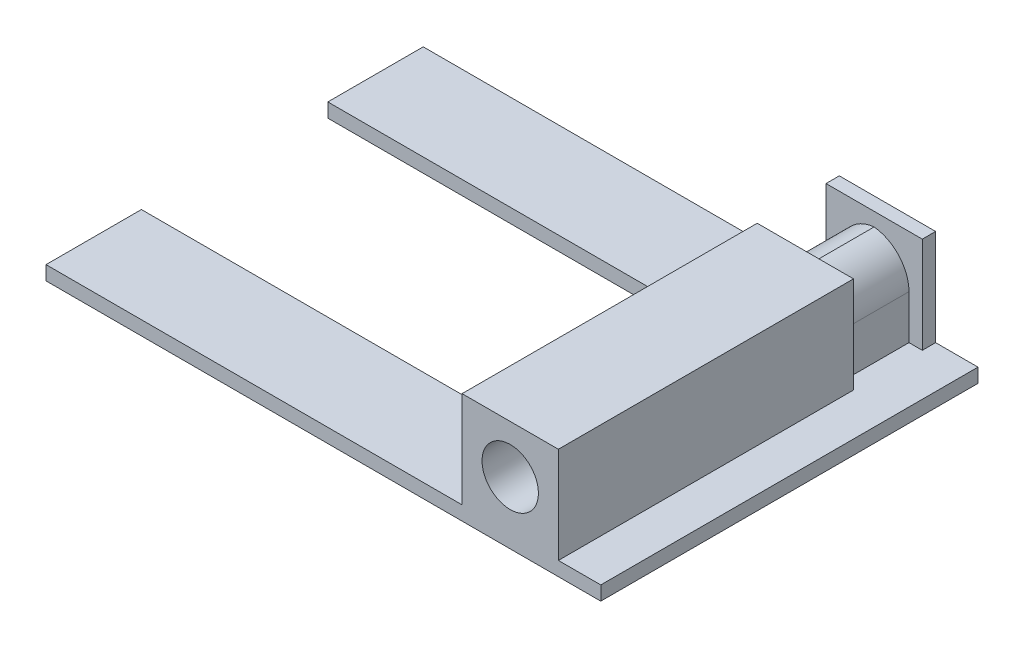
SolidWorks part; units mm, degrees
ref_plane "Front Plane" through (0, 0, 0) normal (0, 0, 1) x (1, 0, 0)
ref_plane "Top Plane" through (0, 0, 0) normal (0, 1, 0) x (1, 0, 0)
ref_plane "Right Plane" through (0, 0, 0) normal (1, 0, 0) x (0, 0, -1)
sketch "Sketch1" plane through (0, 0, 0) normal (0, 1, 0) x (1, 0, 0)
  line L0 (-367.5496, 171.2119) -> (132.4504, 171.2119)
  line L1 (132.4504, 171.2119) -> (132.4504, -168.7881)
  line L2 (132.4504, -168.7881) -> (-367.5496, -168.7881)
  line L3 (-485, 3.2119) -> (-117.5496, -168.7881) construction
  line L4 (0, -0.7881) -> (-367.5496, -168.7881) construction
  line L5 (-301.2748, -82.7881) -> (-367.5496, -82.7881) construction
  line L6 (0, -0.7881) -> (132.4504, -168.7881) construction
  line L7 (-367.5496, -82.7881) -> (132.4504, -82.7881) construction
  line L8 (-367.5496, 171.2119) -> (0, -0.7881) construction
  line L9 (-117.5496, 171.2119) -> (-485, 3.2119) construction
  line L10 (-183.7748, 85.2119) -> (-367.5496, 85.2119) construction
  line L11 (0, -0.7881) -> (132.4504, 171.2119) construction
  line L12 (-183.7748, 85.2119) -> (132.4504, 85.2119) construction
  line L13 (-367.5496, 171.2119) -> (-367.5496, 85.2119)
  line L14 (-117.5496, 171.2119) -> (132.4504, 85.2119) construction
  line L15 (132.4504, 171.2119) -> (0, 85.2119) construction
  line L16 (132.4504, -168.7881) -> (-267.5496, -168.7881) construction
  line L17 (7.4504, 128.2119) -> (7.4504, -82.7881) construction
  line L18 (-367.5496, 85.2119) -> (7.4504, 85.2119) construction
  line L19 (7.4504, 85.2119) -> (7.4504, -82.7881) construction
  line L20 (-367.5496, 85.2119) -> (7.4504, 85.2119)
  line L21 (7.4504, 85.2119) -> (7.4504, -82.7881)
  line L22 (7.4504, -82.7881) -> (-367.5496, -82.7881)
  line L23 (-367.5496, -82.7881) -> (-367.5496, -168.7881)
  line L24 (132.4504, -168.7881) -> (-67.5496, -168.7881) construction
  line L25 (-67.5496, -168.7881) -> (-67.5496, 171.2119) construction
  line L27 (75.2504, 1.2119) -> (49.8504, 1.2119) construction
  line L28 (49.8504, 1.2119) -> (24.4504, 1.2119) construction
  point P15 (-67.5496, 1.2119)
  dimension "D1" = 86
  dimension "D2" = 500
  dimension "D3" = 340
  dimension "D4" = 485
  dimension "D5" = 400
  dimension "D6" = 200
  dimension "D7" = 50.8
  dimension "D8" = 17
extrude "Boss-Extrude1" add sketch "Sketch1" along normal blind 12.7 contours L22 L23 L2 L1 L0 L13 L20 L21
ref_plane "Plane1" through (0, 12.7, 0) normal (0, 1, 0) x (1, 0, 0)
sketch "Sketch3" plane through (0, 12.7, 0) normal (0, 1, 0) x (1, 0, 0)
  line L0 (7.4504, 1.2119) -> (25.4504, 1.2119) construction
  line L1 (7.4504, 85.2119) -> (7.4504, -82.7881) construction
  line L2 (25.4504, 1.2119) -> (76.2504, 1.2119) construction
  line L3 (76.2504, 1.2119) -> (94.2504, 1.2119) construction
  line L4 (50.8504, 1.2119) -> (50.8504, -168.7881) construction
  line L5 (132.4504, -168.7881) -> (-367.5496, -168.7881) construction
  line L6 (50.8504, 1.2119) -> (50.8504, 171.2119) construction
  line L7 (-367.5496, 171.2119) -> (132.4504, 171.2119) construction
  line L8 (94.2504, 1.2119) -> (94.2504, 171.2119) construction
  line L9 (7.4504, 171.2119) -> (7.4504, -168.7881) construction
  line L10 (94.2504, 1.2119) -> (94.2504, -168.7881) construction
  line L11 (25.4504, 1.2119) -> (25.4504, 171.2119) construction
  line L12 (76.2504, 171.2119) -> (76.2504, -168.7881) construction
  line L13 (25.4504, 1.2119) -> (25.4504, -168.7881) construction
  dimension "D1" = 18
  dimension "D2" = 18
  dimension "D3" = 50.8
ref_plane "Plane2" through (0, 0, 168.7881) normal (0, 0, 1) x (1, 0, 0)
sketch "Sketch4" plane through (0, 0, 168.7881) normal (0, 0, 1) x (1, 0, 0)
  line L0 (132.4504, 12.7) -> (-367.5496, 12.7) construction
  line L1 (7.4504, 12.7) -> (94.2504, 12.7)
  line L2 (7.4504, 12.7) -> (7.4504, 99.5)
  line L3 (7.4504, 99.5) -> (94.2504, 99.5)
  line L4 (94.2504, 12.7) -> (94.2504, 99.5)
  line L5 (7.4504, 12.7) -> (94.2504, 99.5) construction
  line L6 (94.2504, 12.7) -> (7.4504, 99.5) construction
  line L7 (25.4504, 12.7) -> (25.4504, 99.5) construction
  circle A0 centre (50.8504, 56.1) radius 25.4
ref_plane "Plane3" through (0, 0, -171.2119) normal (0, 0, -1) x (-1, 0, 0)
extrude "Boss-Extrude3" add sketch "Sketch4" against normal up to vertex (340 mm away) up to point (132.4504, 12.7, -171.2119)
ref_plane "Plane4" through (0, 99.5, 0) normal (0, 1, 0) x (1, 0, 0)
sketch "Sketch6" plane through (0, 99.5, 0) normal (0, 1, 0) x (1, 0, 0)
  line L0 (7.4504, 171.2119) -> (7.4504, 85.2119) construction
  line L1 (7.4504, 85.2119) -> (94.2504, 171.2119) construction
  line L2 (7.4504, 85.2119) -> (94.2504, 85.2119) construction
  line L3 (94.2504, 1.2119) -> (94.2504, 171.2119) construction
  line L4 (94.2504, 85.2119) -> (50.8504, 128.2119) construction
  line L5 (50.8504, 128.2119) -> (7.4504, 171.2119) construction
  line L6 (94.2504, 171.2119) -> (94.2504, 159.2119) construction
  line L7 (94.2504, 159.2119) -> (7.4504, 159.2119) construction
  line L8 (94.2504, 85.2119) -> (94.2504, 97.2119) construction
  line L10 (94.2504, 97.2119) -> (7.4504, 97.2119) construction
  line L12 (7.4504, 159.2119) -> (94.2504, 159.2119)
  line L13 (7.4504, 159.2119) -> (7.4504, 97.2119)
  line L14 (7.4504, 97.2119) -> (94.2504, 97.2119)
  line L15 (94.2504, 159.2119) -> (94.2504, 97.2119)
  dimension "D1" = 12
extrude "Cut-Extrude3" cut sketch "Sketch6" against normal blind 12
ref_plane "Plane9" through (7.4504, 0, 0) normal (-1, 0, 0) x (0, 0, 1)
sketch "Sketch7" plane through (7.4504, 0, 0) normal (-1, 0, 0) x (0, 0, 1)
  line L0 (-159.2119, 87.5) -> (-159.2119, 12.7) construction
  line L1 (-171.2119, 12.7) -> (168.7881, 12.7) construction
  line L2 (-97.2119, 87.5) -> (-97.2119, 12.7) construction
  line L4 (-159.2119, 87.5) -> (-97.2119, 87.5)
  line L5 (-159.2119, 87.5) -> (-159.2119, 12.7)
  line L6 (-159.2119, 12.7) -> (-97.2119, 12.7)
  line L7 (-97.2119, 87.5) -> (-97.2119, 12.7)
extrude "Cut-Extrude4" cut sketch "Sketch7" against normal blind 12 contours L5 L6 L7 L4
ref_plane "Plane10" through (94.2504, 0, 0) normal (1, 0, 0) x (0, 0, -1)
sketch "Sketch8" plane through (94.2504, 0, 0) normal (1, 0, 0) x (0, 0, -1)
  line L0 (159.2119, 87.5) -> (159.2119, 12.7) construction
  line L1 (1.2119, 12.7) -> (171.2119, 12.7) construction
  line L3 (97.2119, 87.5) -> (159.2119, 87.5)
  line L4 (97.2119, 87.5) -> (97.2119, 12.7)
  line L5 (97.2119, 12.7) -> (159.2119, 12.7)
  line L6 (159.2119, 87.5) -> (159.2119, 12.7)
extrude "Cut-Extrude5" cut sketch "Sketch8" against normal blind 12
fillet "Fillet2" radius 35 2 edges at (82.2504, 87.5, -128.2119) (19.4504, 87.5, -128.2119)
